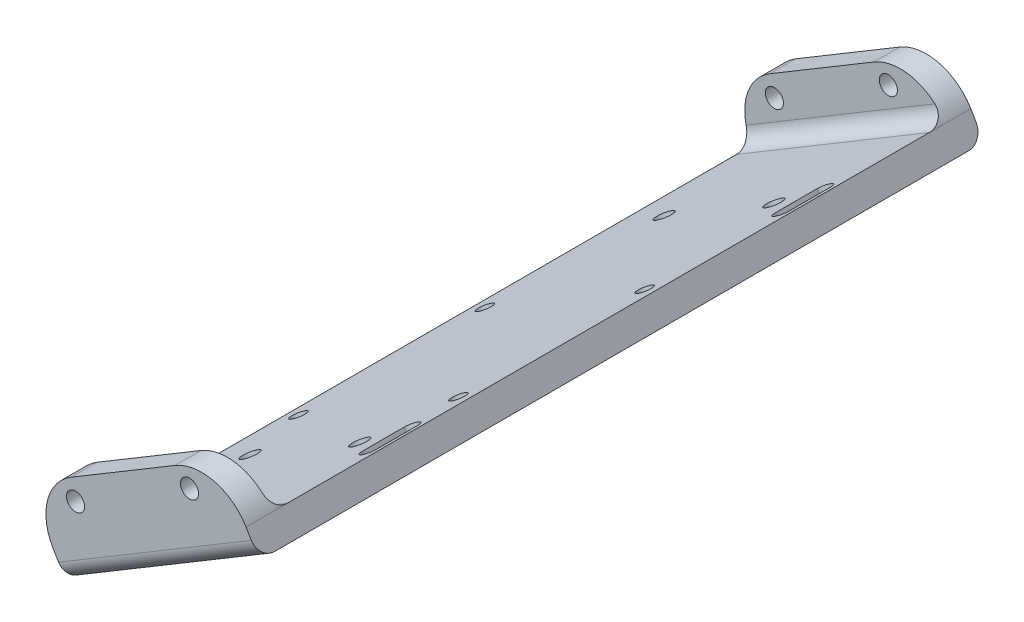
SolidWorks part; units mm, degrees
ref_plane "前视基准面" through (0, 0, 0) normal (0, 0, 1) x (1, 0, 0)
ref_plane "上视基准面" through (0, 0, 0) normal (0, 1, 0) x (1, 0, 0)
ref_plane "右视基准面" through (0, 0, 0) normal (1, 0, 0) x (0, 0, -1)
other "Configuration Table"
sketch "草图2" plane through (-11.7567, -0.7861, 0) normal (0, 0, 1) x (1, 0, 0)
  line L0 (-9.4044, 34.5643) -> (-25.9417, 62.2117) construction
  line L1 (-31.4185, 21.3969) -> (-47.9555, 49.0437) construction
  line L2 (-17.6731, 48.388) -> (-39.687, 35.2203) construction
  line L3 (1.5178, 33.5919) -> (4.0845, 29.301)
  line L4 (-28.68, 41.8042) -> (-38.5, 58.2222) construction
  line L5 (-28.68, 41.8042) -> (-10.0573, 52.9434) construction
  line L6 (-10.0573, 52.9434) -> (25656.3635, -42856.6691) construction
  line L7 (-12.1974, 37.0406) -> (-32.2791, 25.0287)
  line L8 (-35.7277, 11.3135) -> (-33.1611, 7.0225)
  line L9 (-33.1611, 7.0225) -> (4.0845, 29.301)
  line L11 (0.2345, 35.7374) -> (-37.0111, 13.459) construction
  line L12 (1.5178, 33.5919) -> (-35.7277, 11.3135) construction
  arc A0 (-34.1465, 21.0497) -> (-28.7563, 22.0862) centre (-31.4185, 21.3969) ccw construction
  circle A1 centre (-31.4185, 21.3969) radius 1.75
  circle A2 centre (-31.4185, 21.3969) radius 1.75
  circle A3 centre (-9.4044, 34.5643) radius 1.75
  circle A4 centre (-9.4044, 34.5643) radius 1.75
  circle A5 centre (-47.9555, 49.0437) radius 1.75
  circle A6 centre (-47.9555, 49.0437) radius 1.75
  circle A7 centre (-25.9417, 62.2117) radius 1.75
  circle A8 centre (-25.9417, 62.2117) radius 1.75
  arc A9 (-11.271, 32.5448) -> (-7.8081, 36.8035) centre (-9.4044, 34.5643) ccw construction
  arc A10 (-34.1465, 21.0497) -> (-28.7563, 22.0862) centre (-31.4185, 21.3969) ccw construction
  arc A11 (-11.271, 32.5448) -> (-7.8081, 36.8035) centre (-9.4044, 34.5643) ccw construction
  arc A12 (-10.5922, 33.2791) -> (-8.3886, 35.9893) centre (-9.4044, 34.5643) ccw
  arc A13 (-33.1545, 21.1759) -> (-29.7244, 21.8356) centre (-31.4185, 21.3969) ccw
  circle A14 centre (-9.4044, 34.5643) radius 1.75
  circle A15 centre (-31.4185, 21.3969) radius 1.75
  arc A16 (-32.2791, 25.0287) -> (-35.7277, 11.3135) centre (-27.1458, 16.4468) ccw
  arc A17 (-12.1974, 37.0406) -> (1.5178, 33.5919) centre (-7.0641, 28.4587) cw
  point P42 (-3.6155, 42.1739)
  dimension "D6" = 10
  dimension "D5" = 1
  dimension "D7" = 15
  dimension "D1" = 0
  dimension "D2" = 0
  dimension "D3" = 0
  dimension "D4" = 0
extrude "凸台-拉伸1" add sketch "草图2" along normal blind 140 contours A17 L7 A16 L8 L9 L3 A4 A2 region at (-29.8818, 23.3721, 0)
sketch "草图3" plane through (6.9112, 4.1339, 0) normal (0.8582, 0.5133, 0) x (0, 0, -1)
  line L0 (-140, 33.4096) -> (0, 33.4096) construction
  line L1 (-5, 33.4096) -> (-135, 33.4096)
  line L2 (-5, 33.4096) -> (-5, 48.1336)
  line L3 (-5, 48.1336) -> (-135, 48.1336)
  line L4 (-135, 33.4096) -> (-135, 48.1336)
  line L5 (0, 33.4096) -> (0, 43.4096) construction
  line L6 (-140, 43.4096) -> (-140, 33.4096) construction
  dimension "D1" = 5
  dimension "D2" = 5
extrude "切除-拉伸1" cut sketch "草图3" against normal blind 140
fillet "圆角1" radius 3 4 edges at (-28.8617, 21.6666, 5) (-28.8617, 21.6666, 135) (-26.295, 17.3756, 140) (-26.295, 17.3756, 0)
ref_plane "基准面1" through (0, 0, 70) normal (0, 0, -1) x (-1, 0, 0)
sketch "草图4" plane through (-17.1501, 28.6719, 0) normal (-0.5133, 0.8582, 0) x (0.8582, 0.5133, 0)
  arc A0 (4.3532, -58.35) -> (4.3532, -61.25) centre (4.3532, -59.8) ccw
  arc A1 (4.3532, -61.25) -> (4.3532, -58.35) centre (4.3532, -59.8) ccw
  arc A2 (4.3532, -58.55) -> (4.3532, -61.05) centre (4.3532, -59.8) ccw
  arc A3 (4.3532, -61.05) -> (4.3532, -58.55) centre (4.3532, -59.8) ccw
  arc A4 (4.3532, -58.55) -> (4.3532, -61.05) centre (4.3532, -59.8) ccw construction
  arc A5 (4.3532, -61.05) -> (4.3532, -58.55) centre (4.3532, -59.8) ccw construction
  arc A6 (-31.6468, -61.05) -> (-31.6468, -58.55) centre (-31.6468, -59.8) ccw
  arc A7 (-31.6468, -58.55) -> (-31.6468, -61.05) centre (-31.6468, -59.8) ccw
  arc A8 (-31.6468, -61.05) -> (-31.6468, -58.55) centre (-31.6468, -59.8) ccw construction
  arc A9 (-31.6468, -58.55) -> (-31.6468, -61.05) centre (-31.6468, -59.8) ccw construction
  arc A10 (-31.6468, -94.55) -> (-31.6468, -97.05) centre (-31.6468, -95.8) ccw
  arc A11 (-31.6468, -97.05) -> (-31.6468, -94.55) centre (-31.6468, -95.8) ccw
  arc A12 (-31.6468, -94.55) -> (-31.6468, -97.05) centre (-31.6468, -95.8) ccw construction
  arc A13 (-31.6468, -97.05) -> (-31.6468, -94.55) centre (-31.6468, -95.8) ccw construction
  arc A14 (4.3532, -94.55) -> (4.3532, -97.05) centre (4.3532, -95.8) ccw
  arc A15 (4.3532, -97.05) -> (4.3532, -94.55) centre (4.3532, -95.8) ccw
  arc A16 (4.3532, -94.55) -> (4.3532, -97.05) centre (4.3532, -95.8) ccw construction
  arc A17 (4.3532, -97.05) -> (4.3532, -94.55) centre (4.3532, -95.8) ccw construction
  arc A18 (-31.6468, -61.25) -> (-31.6468, -58.35) centre (-31.6468, -59.8) ccw
  arc A19 (-31.6468, -58.35) -> (-31.6468, -61.25) centre (-31.6468, -59.8) ccw
  arc A20 (-31.6468, -94.35) -> (-31.6468, -97.25) centre (-31.6468, -95.8) ccw
  arc A21 (-31.6468, -97.25) -> (-31.6468, -94.35) centre (-31.6468, -95.8) ccw
  arc A22 (4.3532, -94.35) -> (4.3532, -97.25) centre (4.3532, -95.8) ccw
  arc A23 (4.3532, -97.25) -> (4.3532, -94.35) centre (4.3532, -95.8) ccw
  dimension "D1" = 0
  dimension "D2" = 0
  dimension "D3" = 0
  dimension "D4" = 0
  dimension "D5" = 0.2
extrude "切除-拉伸2" cut sketch "草图4" against normal up to surface (5 mm away) contours A22 A23 | A20 A21 | A0 A1 | A18 A19 up to face at (-26.295, 17.3756, 70)
sketch "草图6" plane through (-14.5835, 24.3809, 0) normal (0.5133, -0.8582, 0) x (0.8582, 0.5133, 0)
  line L0 (-35.3468, 137) -> (-35.3468, 3) construction
  line L1 (8.0532, 137) -> (8.0532, 3) construction
  line L2 (-15.8739, 70) -> (15.8739, 70) construction
  circle A0 centre (-26, 110) radius 1.65
  circle A1 centre (-1.2968, 110) radius 1.65
  circle A2 centre (-1.2968, 30) radius 1.65
  circle A3 centre (-26, 30) radius 1.65
  dimension "D1" = 9.3468
  dimension "D2" = 9.35
extrude "切除-拉伸3" cut sketch "草图6" against normal through all
sketch "草图7" plane through (-14.5835, 24.3809, 0) normal (0.5133, -0.8582, 0) x (0.8582, 0.5133, 0)
  line L0 (8.0532, 132) -> (8.0532, 8) construction
  line L1 (3.8532, 11) -> (3.8532, 129) construction
  line L2 (8.0532, 132) -> (8.0532, 8)
  line L3 (3.8532, 11) -> (3.8532, 129)
  line L4 (5.3532, 34.1185) -> (5.3532, 26.1185) construction
  line L5 (6.8532, 34.1185) -> (6.8532, 26.1185)
  line L6 (3.8532, 34.1185) -> (3.8532, 26.1185)
  line L7 (3.8532, 70) -> (16.3298, 70) construction
  line L8 (5.3532, 105.8815) -> (5.3532, 113.8815) construction
  line L9 (6.8532, 105.8815) -> (6.8532, 113.8815)
  line L10 (3.8532, 105.8815) -> (3.8532, 113.8815)
  arc A0 (6.8532, 34.1185) -> (3.8532, 34.1185) centre (5.3532, 34.1185) ccw
  circle A1 centre (-1.2968, 110) radius 1.65
  circle A2 centre (-1.2968, 110) radius 1.65 construction
  circle A3 centre (-1.2968, 30) radius 1.65
  circle A4 centre (-1.2968, 30) radius 1.65 construction
  arc A5 (3.8532, 26.1185) -> (6.8532, 26.1185) centre (5.3532, 26.1185) ccw
  arc A6 (6.8532, 105.8815) -> (3.8532, 105.8815) centre (5.3532, 105.8815) cw
  arc A7 (3.8532, 113.8815) -> (6.8532, 113.8815) centre (5.3532, 113.8815) cw
  point P12 (5.3532, 30.1185)
  point P21 (5.3532, 109.8815)
  dimension "D3" = 3
  dimension "D4" = 8
  dimension "D5" = 0
  dimension "D1" = 0
  dimension "D2" = 0
extrude "切除-拉伸5" cut sketch "草图7" against normal through all contours L3 A5 L5 A0 | L9 A7 L10 A6 region at (-9.9894, 27.1289, 30.1185)
